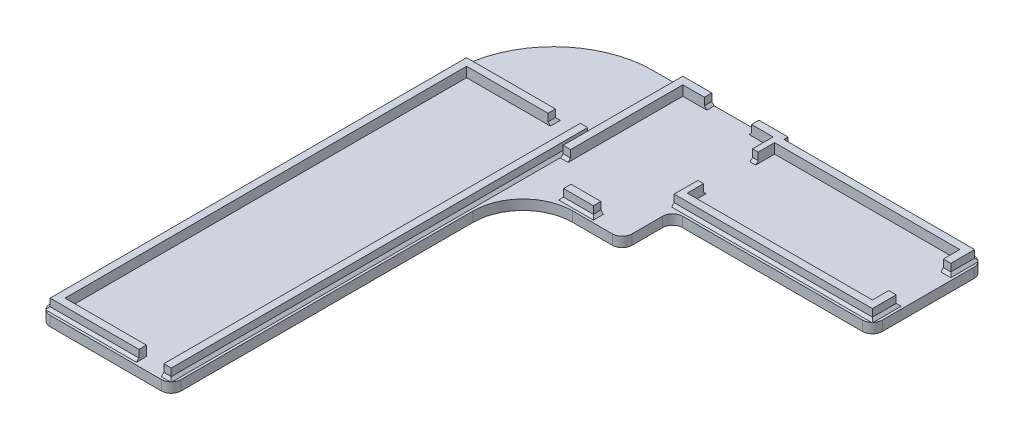
SolidWorks part; units mm, degrees
ref_plane "Front Plane" through (0, 0, 0) normal (0, 0, 1) x (1, 0, 0)
ref_plane "Top Plane" through (0, 0, 0) normal (0, 1, 0) x (1, 0, 0)
ref_plane "Right Plane" through (0, 0, 0) normal (1, 0, 0) x (0, 0, -1)
sketch "Sketch1" plane through (0, 0, 0) normal (0, 1, 0) x (1, 0, 0)
  line L0 (-53.9919, 36.7578) -> (-75.3919, 36.7578)
  line L1 (-75.3919, 36.7578) -> (-75.3919, -44.1422)
  line L2 (-75.3919, -44.1422) -> (-53.9919, -44.1422)
  line L3 (-53.9919, -44.1422) -> (-53.9919, 36.7578)
  line L4 (-75.0919, -43.8422) -> (-54.2919, -43.8422)
  line L5 (-54.2919, -43.8422) -> (-54.2919, 36.4578)
  line L6 (-54.2919, 36.4578) -> (-75.0919, 36.4578)
  line L7 (-75.0919, 36.4578) -> (-75.0919, -43.8422)
  line L8 (-75.0919, -43.8422) -> (-54.2919, -43.8422)
  line L9 (-54.2919, -43.8422) -> (-54.2919, 36.4578)
  line L10 (-54.2919, 36.4578) -> (-75.0919, 36.4578)
  line L11 (-75.0919, 36.4578) -> (-75.0919, -43.8422)
  line L12 (-52.4919, 38.2578) -> (-76.8919, 38.2578)
  line L13 (-76.8919, 38.2578) -> (-76.8919, -45.6422)
  line L14 (-76.8919, -45.6422) -> (-52.4919, -45.6422)
  line L15 (-52.4919, -45.6422) -> (-52.4919, 38.2578)
  line L16 (-50.383, 55.3) -> (-50.383, 32.7)
  line L17 (-44.283, 26.7) -> (-38.283, 26.7)
  line L18 (-32.183, 32.7) -> (-32.183, 40.1551)
  line L19 (-32.183, 55.3) -> (-50.383, 55.3)
  line L20 (-50.083, 27) -> (-32.483, 27)
  line L21 (-32.483, 27) -> (-32.483, 55)
  line L22 (-32.483, 55) -> (-50.083, 55)
  line L23 (-50.083, 55) -> (-50.083, 27)
  line L25 (-32.483, 32.7) -> (-32.483, 40.1551)
  line L26 (-32.483, 55) -> (-50.083, 55)
  line L27 (-50.083, 55) -> (-50.083, 32.7)
  line L28 (-30.683, 56.8) -> (-51.883, 56.8)
  line L29 (-51.883, 56.8) -> (-51.883, 32.7)
  line L30 (-44.283, 25.2) -> (-38.283, 25.2)
  line L31 (-30.683, 32.7) -> (-30.683, 37.1551)
  line L32 (-41.283, 60.3419) -> (-41.283, 21.4937) construction
  line L33 (-46.033, 56.8) -> (-46.033, 55.3)
  line L34 (-36.533, 56.8) -> (-36.533, 55.3)
  line L35 (6.2634, 54.4551) -> (-31.0366, 54.4551)
  line L36 (-31.0366, 54.4551) -> (-31.0366, 51.1551)
  line L37 (-31.0366, 36.8551) -> (6.2634, 36.8551)
  line L38 (6.2634, 36.8551) -> (6.2634, 40.1551)
  line L39 (5.9634, 37.1551) -> (5.9634, 54.1551)
  line L40 (5.9634, 54.1551) -> (-30.7366, 54.1551)
  line L41 (-30.7366, 54.1551) -> (-30.7366, 37.1551)
  line L42 (-30.7366, 37.1551) -> (5.9634, 37.1551)
  line L44 (5.9634, 54.1551) -> (-30.7366, 54.1551)
  line L46 (-30.7366, 37.1551) -> (5.9634, 37.1551)
  line L47 (7.7634, 55.9551) -> (-32.5366, 55.9551)
  line L48 (-32.5366, 55.9551) -> (-32.5366, 51.1551)
  line L49 (-32.5366, 35.3551) -> (7.7634, 35.3551)
  line L50 (7.7634, 35.3551) -> (7.7634, 40.1551)
  line L51 (6.2634, 51.1551) -> (7.7634, 51.1551)
  line L52 (7.7634, 45.6551) -> (-29.0417, 45.6551) construction
  line L53 (6.2634, 40.1551) -> (7.7634, 40.1551)
  line L54 (-12.3866, 55.9551) -> (-12.3866, 35.3551) construction
  line L55 (-31.0366, 40.1551) -> (-32.5366, 40.1551)
  line L56 (-31.0366, 51.1551) -> (-32.5366, 51.1551)
  line L57 (-51.883, 32.7) -> (-30.683, 32.7)
  line L58 (-44.283, 26.7) -> (-44.283, 25.2)
  line L59 (-38.283, 26.7) -> (-38.283, 25.2)
  line L60 (-50.083, 55) -> (-50.083, 27) construction
  line L61 (-50.383, 55.3) -> (-50.383, 26.7) construction
  line L62 (-51.883, 56.8) -> (-51.883, 25.2) construction
  line L63 (-50.083, 27) -> (-32.483, 27) construction
  line L64 (-50.383, 26.7) -> (-32.183, 26.7) construction
  line L65 (-51.883, 25.2) -> (-30.683, 25.2) construction
  line L66 (-32.483, 27) -> (-32.483, 55) construction
  line L67 (-32.183, 26.7) -> (-32.183, 55.3) construction
  line L68 (-30.683, 25.2) -> (-30.683, 56.8) construction
  line L69 (-30.683, 54.1551) -> (-30.683, 56.8)
  line L70 (-30.7366, 54.1551) -> (-30.7366, 37.1551) construction
  line L71 (-31.0366, 40.1551) -> (-31.0366, 36.8551)
  line L72 (-31.0366, 54.4551) -> (-31.0366, 36.8551) construction
  line L73 (-32.183, 51.1551) -> (-32.183, 55.3)
  line L74 (-32.483, 51.1551) -> (-32.483, 55)
  line L75 (-32.5366, 40.1551) -> (-32.5366, 35.3551)
  line L76 (-32.5366, 55.9551) -> (-32.5366, 35.3551) construction
  line L77 (7.7634, 51.1551) -> (7.7634, 55.9551)
  line L78 (7.7634, 35.3551) -> (7.7634, 55.9551) construction
  line L79 (6.2634, 51.1551) -> (6.2634, 54.4551)
  line L80 (6.2634, 36.8551) -> (6.2634, 54.4551) construction
  line L81 (5.9634, 37.1551) -> (5.9634, 54.1551) construction
  line L82 (-53.9919, -44.1422) -> (-53.9919, -45.6422)
  line L83 (-58.9919, -44.1422) -> (-58.9919, -45.6422)
  line L84 (-53.9919, 36.7578) -> (-53.9919, 38.2578)
  line L85 (-58.9919, 36.7578) -> (-58.9919, 38.2578)
  point P30 (-41.283, 55.3)
  dimension "D7" = 9.5
  dimension "D11" = 11
  dimension "D12" = 6
  dimension "D13" = 6
  dimension "D14" = 5
  dimension "D15" = 5
  dimension "D1" = 0
  dimension "D2" = 0.3
  dimension "D3" = 1.5
  dimension "D4" = 0
  dimension "D5" = 0.3
  dimension "D6" = 1.5
  dimension "D8" = 0
  dimension "D9" = 0.3
  dimension "D10" = 1.5
extrude "Boss-Extrude1" add sketch "Sketch1" along normal blind 4 contours L0 L85 L12 L13 L14 L83 L2 L1 | L84 L3 L82 L14 L15 L12 | L29 L57 L16 L19 L33 L28 | L47 L69 L28 L34 L19 L48 | L73 L56 L36 L35 L69 L47 L48 L19 | L59 L17 L58 L30 | L53 L38 L37 L31 L49 L50 | L71 L55 L18 L49 L31 L37 | L79 L51 L77 L47 L69 L35 region at (-53.2419, 0, 3.6922) region at (-67.1919, 0, -37.6157) region at (-50.6858, 0, -46.4778) region at (-33.9289, 0, -56.1178) region at (-31.5741, 0, -53.7714) region at (-31.5439, 0, -37.61) region at (-9.9995, 0, -55.0154) region at (-9.9995, 0, -36.2948) region at (-41.283, 0, -25.95)
sketch "Sketch2" plane through (0, 0, 0) normal (0, 1, 0) x (1, 0, 0)
  line L0 (-76.8919, 38.2578) -> (-76.8919, -45.6422) construction
  line L1 (-57.8919, 56.8) -> (6.7634, 56.8)
  line L2 (-77.8919, 36.8) -> (-77.8919, -44.6422)
  line L3 (-75.8919, -46.6422) -> (-53.4919, -46.6422)
  line L4 (8.7634, 54.8) -> (8.7634, 36.3551)
  line L5 (-46.033, 56.8) -> (-51.883, 56.8) construction
  line L6 (7.7634, 51.1551) -> (7.7634, 55.9551) construction
  line L7 (-76.8919, -45.6422) -> (-58.9919, -45.6422) construction
  line L8 (-51.4919, -44.6422) -> (-51.4919, 14.2)
  line L9 (-41.4919, 24.2) -> (-33.483, 24.2)
  line L10 (-52.4919, -45.6422) -> (-52.4919, 38.2578) construction
  line L11 (-44.283, 25.2) -> (-38.283, 25.2) construction
  line L12 (-31.483, 26.2) -> (-31.483, 32.3551)
  line L13 (-29.483, 34.3551) -> (6.7634, 34.3551)
  line L14 (-32.183, 35.3551) -> (7.7634, 35.3551) construction
  line L15 (-32.483, 27) -> (-32.483, 55) construction
  arc A0 (-57.8919, 56.8) -> (-77.8919, 36.8) centre (-57.8919, 36.8) ccw
  arc A1 (-51.4919, 14.2) -> (-41.4919, 24.2) centre (-41.4919, 14.2) cw
  arc A2 (6.7634, 56.8) -> (8.7634, 54.8) centre (6.7634, 54.8) cw
  arc A3 (-77.8919, -44.6422) -> (-75.8919, -46.6422) centre (-75.8919, -44.6422) ccw
  arc A4 (-51.4919, -44.6422) -> (-53.4919, -46.6422) centre (-53.4919, -44.6422) cw
  arc A5 (6.7634, 34.3551) -> (8.7634, 36.3551) centre (6.7634, 36.3551) ccw
  arc A6 (-31.483, 32.3551) -> (-29.483, 34.3551) centre (-29.483, 32.3551) cw
  arc A7 (-31.483, 26.2) -> (-33.483, 24.2) centre (-33.483, 26.2) cw
  dimension "D6" = 20
  dimension "D7" = 10
  dimension "D10" = 2
  dimension "D1" = 1
  dimension "D2" = 1
  dimension "D3" = 1
  dimension "D4" = 1
  dimension "D5" = 1
  dimension "D8" = 1
  dimension "D9" = 1
extrude "Boss-Extrude2" add sketch "Sketch2" along normal blind 2
chamfer "Chamfer1" distance 0.5 angle 45 21 edges at (-31.6098, 2, -40.1551) (-31.6098, 2, -51.1551) (-36.533, 2, -56.05) (-46.033, 2, -56.05) (7.0134, 2, -51.1551) (-11.4598, 2, -55.9551) (7.7634, 2, -53.5551) (7.0134, 2, -40.1551) (7.7634, 2, -37.7551) (-12.2098, 2, -35.3551) (-44.283, 2, -25.95) (-38.283, 2, -25.95) (-41.283, 2, -25.2) (-51.133, 2, -32.7) (-53.2419, 2, -38.2578) (-53.2419, 2, 45.6422) (-52.4919, 2, 3.6922) (-58.9919, 2, -37.5078) (-67.9419, 2, 45.6422) (-67.9419, 2, -38.2578) (-76.8919, 2, 3.6922)
